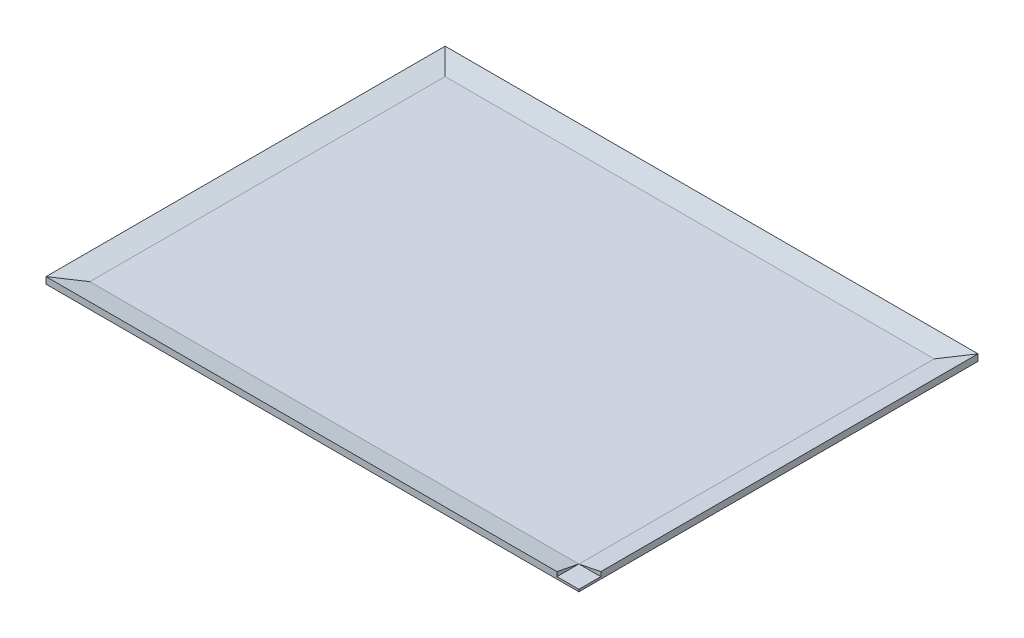
SolidWorks part; units mm, degrees
ref_plane "Спереди" through (0, 0, 0) normal (0, 0, 1) x (1, 0, 0)
ref_plane "Сверху" through (0, 0, 0) normal (0, 1, 0) x (1, 0, 0)
ref_plane "Справа" through (0, 0, 0) normal (1, 0, 0) x (0, 0, -1)
ref_plane "Плоскость4"
sketch "Эскиз1" plane through (0, 0, 0) normal (0, 1, 0) x (-1, 0, 0)
  line L0 (1215, 910) -> (-1215, 910)
  line L1 (-1215, 910) -> (-1215, -910)
  line L2 (-1215, -910) -> (1215, -910)
  line L3 (1215, -910) -> (1215, 910)
  dimension "D1" = 2430
  dimension "D2" = 1820
extrude "Выдавливание2" add sketch "Эскиз1" against normal blind 10
ref_plane "Плоскость5"
sketch "Эскиз2" plane through (0, 0, 0) normal (0, 0, 1) x (1, 0, 0)
  line L0 (-1115, 0) -> (-1215, 20)
  line L1 (-1215, 20) -> (-1215, 0)
  line L2 (-1215, 0) -> (-1115, 0)
  dimension "D1" = 20
sketch3d "Трехмерный эскиз1"
  line L0 (-1115, 0, 810) -> (-1115, 0, 0)
  line L1 (1115, 0, 810) -> (-1115, 0, 810)
sweep "По траектории1" add profiles "Эскиз2" path "Трехмерный эскиз1"
sketch3d "Трехмерный эскиз2"
  line L0 (1115, 0, -810) -> (1115, 0, 810)
  line L1 (-1115, 0, -810) -> (1115, 0, -810)
  line L2 (-1115, 0, 0) -> (-1115, 0, -810)
sweep "Сдвиг1" add profiles "Эскиз2<2>" path "Трехмерный эскиз2"
sketch "Эскиз2<2>" plane through (0, 0, 0) normal (0, 0, 1) x (1, 0, 0) same geometry as "Эскиз2"
